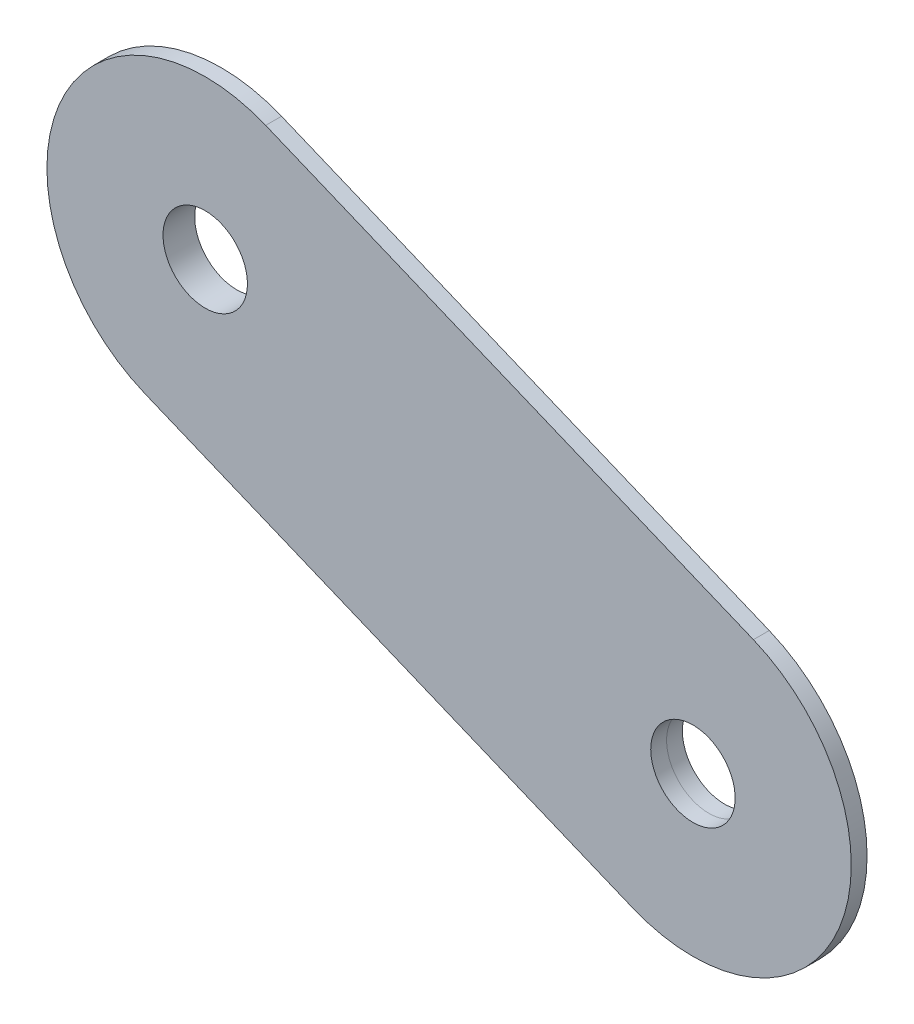
SolidWorks part; units mm, degrees
ref_plane "Front Plane" through (0, 0, 0) normal (0, 0, 1) x (1, 0, 0)
ref_plane "Top Plane" through (0, 0, 0) normal (0, 1, 0) x (1, 0, 0)
ref_plane "Right Plane" through (0, 0, 0) normal (1, 0, 0) x (0, 0, -1)
sketch "Sketch1" plane through (0, 0, 0) normal (0, 0, 1) x (1, 0, 0)
  line L0 (0, 0) -> (46.2112, -19.0925) construction
  line L1 (23.1056, -9.5462) -> (26.6464, -0.9762) construction
  circle A0 centre (0, 0) radius 7.5
  circle A1 centre (0, 0) radius 4
  circle A2 centre (0, 0) radius 4 construction
  circle A3 centre (46.2112, -19.0925) radius 4
  circle A4 centre (46.2112, -19.0925) radius 7.5
  dimension "D1" = 15
extrude "Boss-Extrude1" add sketch "Sketch1" along normal blind 1.5
sketch "Sketch2" plane through (0, 0, 1.5) normal (0, 0, 1) x (1, 0, 0)
  line L0 (0, 0) -> (46.2112, -19.0925) construction
  line L1 (23.1056, -9.5462) -> (26.4754, -1.39) construction
  line L2 (5.7277, 13.8634) -> (51.939, -5.2291)
  line L3 (-5.7277, -13.8634) -> (40.4835, -32.9558)
  arc A0 (5.7277, 13.8634) -> (-5.7277, -13.8634) centre (0, 0) ccw
  circle A1 centre (0, 0) radius 4
  circle A2 centre (0, 0) radius 4 construction
  circle A3 centre (46.2112, -19.0925) radius 4
  arc A4 (51.939, -5.2291) -> (40.4835, -32.9558) centre (46.2112, -19.0925) cw
  point P1 (-5.7277, -13.8634)
  dimension "D1" = 30
extrude "Boss-Extrude2" add sketch "Sketch2" along normal blind 1.5
